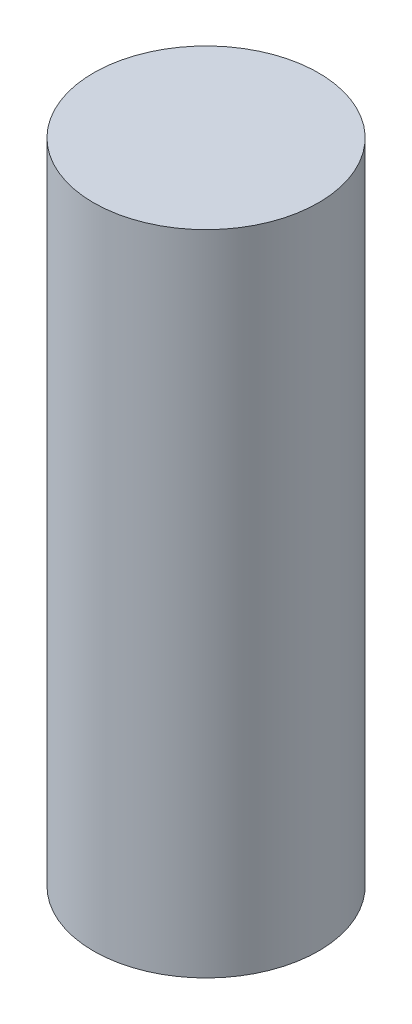
SolidWorks part; units mm, degrees
material "6061-T6 (SS)"
ref_plane "Front Plane" through (0, 0, 0) normal (1, 0, 0) x (0, 1, 0)
ref_plane "Top Plane" through (0, 0, 0) normal (0, 0, 1) x (0, 1, 0)
ref_plane "Right Plane" through (0, 0, 0) normal (0, 1, 0) x (-1, 0, 0)
sketch "Sketch1" [suppressed] plane through (0, 0, 0) normal (1, 0, 0) x (0, 1, 0)
  line L0 (0, 0) -> (-28.8256, 0)
  line L1 (-26.9494, 6.35) -> (-24.4094, 6.35)
  line L2 (-24.4094, 6.35) -> (-24.4094, 4)
  line L3 (-24.4094, 4) -> (0, 4)
  line L5 (0, 4) -> (0, 0)
  line L6 (-17.399, 0) -> (-17.399, 4) construction
  arc A0 (-28.8256, 0) -> (-26.9494, 6.35) centre (-17.1416, 0) cw
  dimension "D6" = 11.684
  dimension "D1" = 4
  dimension "D2" = 6.35
  dimension "D5" = 2.54
  dimension "D3" = 7.0104
  dimension "D4" = 17.399
revolve "Revolve1" [suppressed] add sketch "Sketch1" angle 360 about L0
sketch "Sketch2" plane through (0, 0, 0) normal (0, 1, 0) x (-1, 0, 0)
  circle A0 centre (0, 0) radius 3.175
  dimension "D1" = 6.35
extrude "Boss-Extrude1" add sketch "Sketch2" along normal blind 18.288
equation "\"D1@Sketch1\"=4mm"
equation "\"Wheel Wdith\"= 0.276"
equation "\"wall thickness\"= 0.225"
equation "\"nut thickness\"= 0.23"
equation "\"D3@Sketch1\"=\"Wheel Wdith\""
equation "\"D4@Sketch1\"=\"nut thickness\"*2+\"wall thickness\""
